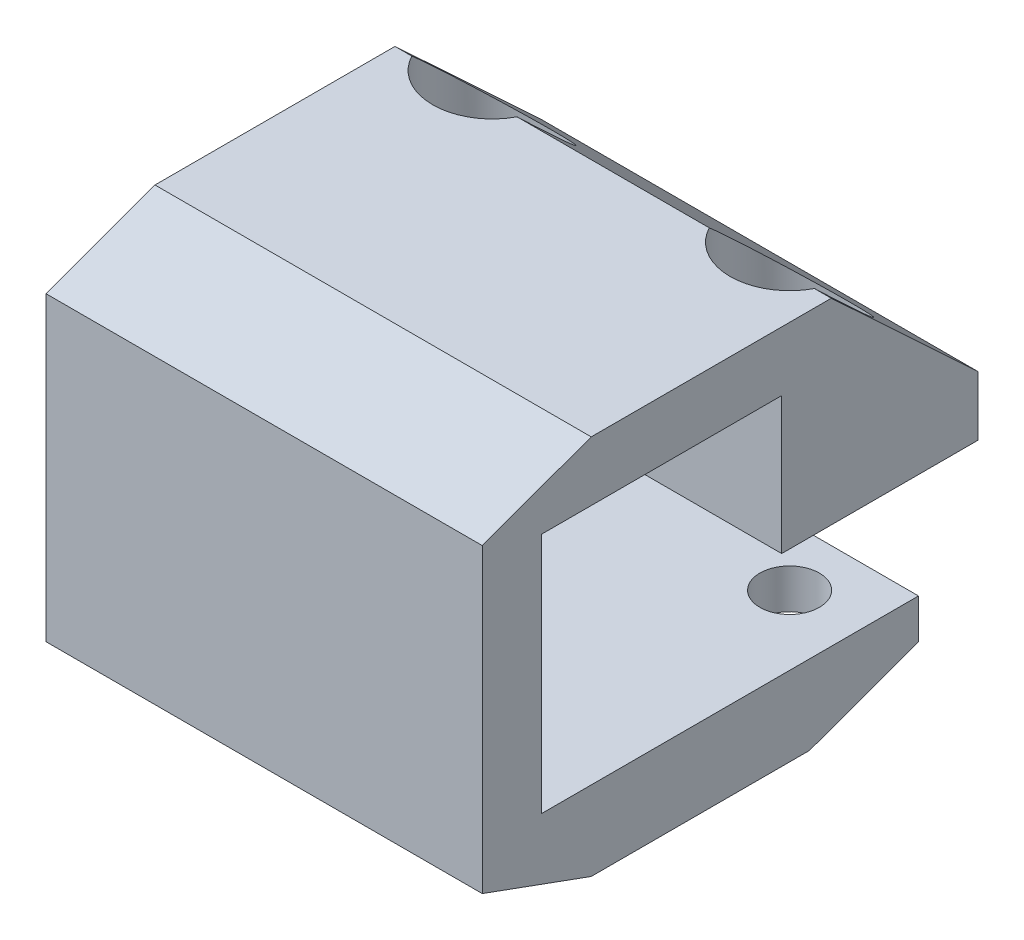
SolidWorks part; units mm, degrees
ref_plane "Alzado" through (0, 0, 0) normal (0, 0, 1) x (1, 0, 0)
ref_plane "Planta" through (0, 0, 0) normal (0, 1, 0) x (1, 0, 0)
ref_plane "Vista lateral" through (0, 0, 0) normal (1, 0, 0) x (0, 0, -1)
sketch "Croquis1" plane through (0, 0, 0) normal (1, 0, 0) x (0, 0, -1)
  line L0 (0, -3.6787) -> (10.9196, -3.6787)
  line L1 (10.9196, -3.6787) -> (10.9196, -7.6787)
  line L2 (10.9196, -7.6787) -> (-11.0804, -7.6787)
  line L3 (-11.0804, -7.6787) -> (-11.0804, 11.5213)
  line L4 (-11.0804, 11.5213) -> (6.5196, 11.5213)
  line L6 (13.9196, 1.6213) -> (4.0196, 1.6213)
  line L7 (4.0196, 1.6213) -> (4.0196, 8.5213)
  line L8 (4.0196, 8.5213) -> (-8.0804, 8.5213)
  line L9 (-8.0804, 8.5213) -> (-8.0804, -3.6787)
  line L10 (-8.0804, -3.6787) -> (0, -3.6787)
  line L11 (13.9196, 1.6213) -> (13.9196, 4.6213)
  line L12 (13.9196, 4.6213) -> (6.5196, 11.5213)
  dimension "D1" = 4
  dimension "D2" = 19
  dimension "D3" = 3
  dimension "D4" = 3
  dimension "D5" = 5.3
  dimension "D6" = 12.1
  dimension "D7" = 12.2
  dimension "D8" = 2.5
  dimension "D9" = 3
  dimension "D10" = 3
extrude "Saliente-Extruir1" add sketch "Croquis1" along normal blind 22
sketch "Croquis2" plane through (0, -7.6787, 0) normal (0, -1, 0) x (1, 0, 0)
  line L0 (11, -7.9196) -> (11, -10.9196) construction
  line L2 (3.5, -7.9196) -> (18.5, -7.9196) construction
  line L3 (22, -10.9196) -> (0, -10.9196) construction
  circle A0 centre (3.5, -7.9196) radius 1.5
  circle A1 centre (18.5, -7.9196) radius 1.5
  point P7 (11, -7.9196)
  dimension "D3" = 3
  dimension "D1" = 3
  dimension "D2" = 15
extrude "Cortar-Extruir1" cut sketch "Croquis2" against normal through all contours A0 | A1
sketch "Croquis3" plane through (22, 0, 0) normal (1, 0, 0) x (0, 0, -1)
  line L0 (-8.0804, 8.5213) -> (-8.0804, 3.5213)
  line L2 (-2.0304, 8.5213) -> (-2.0304, 3.5213) construction
  line L3 (-8.0804, 8.5213) -> (4.0196, 8.5213) construction
  line L4 (-8.0804, 8.5213) -> (-5.4366, 8.5213)
  line L5 (4.0196, 8.5213) -> (4.0196, 3.5213)
  line L6 (1.3759, 8.5213) -> (4.0196, 8.5213)
  arc A0 (4.0196, 3.5213) -> (1.3759, 8.5213) centre (-2.0304, 3.5213) ccw
  arc A1 (-5.4366, 8.5213) -> (-8.0804, 3.5213) centre (-2.0304, 3.5213) ccw
  dimension "D2" = 5
extrude "Saliente-Extruir2" add sketch "Croquis3" against normal offset from surface (4 mm away) 9 from offset 9 up to face at (0, 2.294, -2.356) offset against normal yes
chamfer "Chaflán1" distance 2 angle 70 1 edges at (11, -7.6787, -10.9196) first distance on face at (11, -5.6787, -10.9196)
sketch "Croquis4" plane through (0, -7.6787, 0) normal (0, -1, 0) x (1, 0, 0)
  line L1 (3.5, -4.6865) -> (0.7, -6.3031)
  line L2 (0.7, -6.3031) -> (0.7, -9.5362)
  line L3 (0.7, -9.5362) -> (3.5, -11.1528)
  line L4 (3.5, -11.1528) -> (6.3, -9.5362)
  line L5 (6.3, -9.5362) -> (6.3, -6.3031)
  line L6 (6.3, -6.3031) -> (3.5, -4.6865)
  line L7 (18.5, -4.6865) -> (15.7, -6.3031)
  line L8 (15.7, -6.3031) -> (15.7, -9.5362)
  line L9 (15.7, -9.5362) -> (18.5, -11.1528)
  line L10 (18.5, -11.1528) -> (21.3, -9.5362)
  line L11 (21.3, -9.5362) -> (21.3, -6.3031)
  line L12 (21.3, -6.3031) -> (18.5, -4.6865)
  circle A0 centre (3.5, -7.9196) radius 2.8 construction
  circle A1 centre (18.5, -7.9196) radius 2.8 construction
  dimension "D1" = 5.6
  dimension "D2" = 5.6
extrude "Cortar-Extruir2" cut sketch "Croquis4" against normal blind 2
chamfer "Chaflán2" distance 2 angle 70 2 edges at (11, 11.5213, 11.0804) (11, -7.6787, 11.0804) first distance on face at (11, 1.9213, 11.0804)
sketch "Croquis5" plane through (0, 11.5213, 0) normal (0, 1, 0) x (1, 0, 0)
  circle A0 centre (3.5, 7.9196) radius 3
  circle A1 centre (18.5, 7.9196) radius 3
  dimension "D1" = 6
extrude "Cortar-Extruir3" cut sketch "Croquis5" against normal offset from surface (6.9 mm away) 3 up to face at (3.5, 1.6213, -6.4196)
